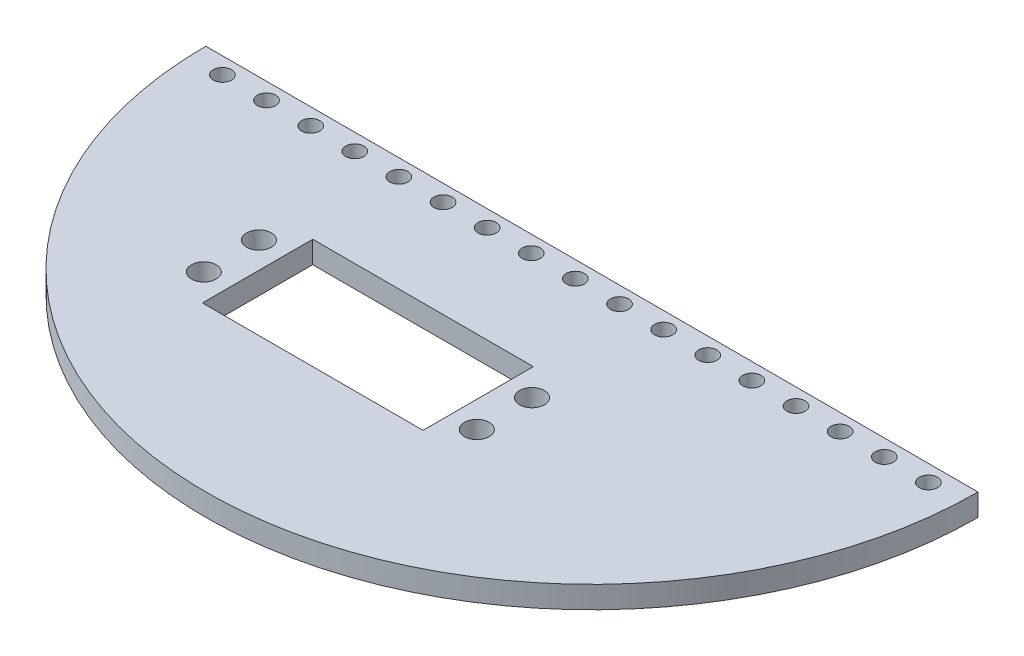
SolidWorks part; units mm, degrees
ref_plane "前视基准面" through (0, 0, 0) normal (0, 0, 1) x (1, 0, 0)
ref_plane "上视基准面" through (0, 0, 0) normal (0, 1, 0) x (1, 0, 0)
ref_plane "右视基准面" through (0, 0, 0) normal (1, 0, 0) x (0, 0, -1)
sketch "草图1" plane through (0, 0, 0) normal (0, 1, 0) x (1, 0, 0)
  line L0 (-50, 0) -> (50, 0)
  arc A0 (50, 0) -> (-50, 0) centre (0, 0) cw
extrude "凸台-拉伸1" add sketch "草图1" along normal blind 4
sketch "草图2" plane through (0, 4, 0) normal (0, 1, 0) x (1, 0, 0)
  line L2 (0, -10.623) -> (10, -10.623)
  line L3 (10, -10.623) -> (10, -30.623)
  line L4 (10, -30.623) -> (-30, -30.623)
  line L5 (-30, -30.623) -> (-30, -10.623)
  line L6 (-30, -10.623) -> (0, -10.623)
extrude "切除-拉伸1" cut sketch "草图2" against normal blind 10
sketch "草图3" plane through (0, 4, 0) normal (0, 1, 0) x (1, 0, 0)
  circle A0 centre (-34.75, -15.623) radius 2.25
  circle A1 centre (-34.75, -25.623) radius 2.25
  circle A2 centre (14.75, -25.623) radius 2.25
  circle A3 centre (14.75, -15.623) radius 2.25
extrude "切除-拉伸2" cut sketch "草图3" against normal blind 10
sketch "草图4" plane through (0, 4, 0) normal (0, 1, 0) x (1, 0, 0)
  circle A0 centre (0, -3) radius 1.65
  circle A1 centre (8, -3) radius 1.65
  circle A2 centre (16, -3) radius 1.65
  circle A3 centre (24, -3) radius 1.65
  circle A4 centre (32, -3) radius 1.65
  circle A5 centre (40, -3) radius 1.65
  circle A6 centre (-40, -3) radius 1.65
  circle A7 centre (-32, -3) radius 1.65
  circle A8 centre (-24, -3) radius 1.65
  circle A9 centre (-16, -3) radius 1.65
  circle A10 centre (-8, -3) radius 1.65
extrude "切除-拉伸3" cut sketch "草图4" against normal blind 10
sketch "草图5" plane through (0, 4, 0) normal (0, 1, 0) x (1, 0, 0)
  line L0 (-70, 0) -> (70, 0)
  circle A0 centre (0, 0) radius 70
  circle A1 centre (0, 0) radius 50
  arc M20 (-50, 0) -> (50, 0) centre (0, 0) ccw
extrude "凸台-拉伸2" add sketch "草图5" against normal blind 4 contours L0 A0 M20 region at (-60, 4, 1.5652)
sketch "草图6" plane through (0, 4, 0) normal (0, 1, 0) x (1, 0, 0)
  circle A0 centre (0, -3) radius 1.65
  circle A1 centre (8, -3) radius 1.65
  circle A2 centre (16, -3) radius 1.65
  circle A3 centre (24, -3) radius 1.65
  circle A4 centre (32, -3) radius 1.65
  circle A5 centre (40, -3) radius 1.65
  circle A6 centre (48, -3) radius 1.65
  circle A7 centre (56, -3) radius 1.65
  circle A8 centre (64, -3) radius 1.65
  circle A9 centre (-8, -3) radius 1.65
  circle A10 centre (-16, -3) radius 1.65
  circle A11 centre (-24, -3) radius 1.65
  circle A12 centre (-32, -3) radius 1.65
  circle A13 centre (-40, -3) radius 1.65
  circle A14 centre (-48, -3) radius 1.65
  circle A15 centre (-56, -3) radius 1.65
  circle A16 centre (-64, -3) radius 1.65
  dimension "D1" = 9
  dimension "D2" = 8
extrude "切除-拉伸4" cut sketch "草图6" against normal blind 4
sketch "草图7" plane through (0, 4, 0) normal (0, 1, 0) x (1, 0, 0)
  line L1 (-30, -20.623) -> (-30, -30.623)
  line L2 (10, -20.623) -> (10, -30.623)
  line L3 (-30, -30.623) -> (10, -30.623)
  line L4 (-30, -10.623) -> (-30, -30.623) construction
  line L5 (10, -30.623) -> (10, -10.623) construction
  line L7 (-30, -20.623) -> (10, -20.623)
  line L8 (-30, -20.623) -> (-30, -40.623)
  line L9 (10, -20.623) -> (10, -40.623)
  line L10 (-30, -40.623) -> (10, -40.623)
  line L11 (-34.75, -15.623) -> (14.75, -15.623)
  line L12 (14.75, -15.623) -> (14.75, -25.623)
  line L13 (14.75, -25.623) -> (14.75, -35.623)
  line L14 (-34.75, -15.623) -> (-34.75, -25.623)
  line L15 (-34.75, -25.623) -> (-34.75, -35.623)
  circle A1 centre (-34.75, -35.623) radius 2.25
  circle A2 centre (14.75, -35.623) radius 2.25
  line M30 (10, -30.623) -> (-30, -30.623)
extrude "切除-拉伸5" cut sketch "草图7" against normal blind 4 contours A1 | L8 L10 L9 M30 | A2 region at (-10, 4, 35.623) region at (16.296, 4, 34.0771) region at (-33.204, 4, 34.0771)
sketch "草图8" plane through (0, 4, 0) normal (0, 1, 0) x (1, 0, 0)
  line L0 (-34.75, -15.623) -> (14.75, -15.623)
  line L1 (14.75, -15.623) -> (14.75, -25.623)
  line L2 (14.75, -25.623) -> (14.75, -20.623)
  line L3 (14.75, -20.623) -> (-41.5549, -20.623)
  line L4 (-41.5549, -20.623) -> (-41.5549, -8.5064)
  line L5 (-41.5549, -8.5064) -> (21.0409, -8.9873)
  line L6 (21.0409, -8.9873) -> (21.0409, -20.623)
  line L7 (21.0409, -20.623) -> (14.75, -20.623)
  line M3 (-30, -40.623) -> (-30, -10.623)
  line M4 (-30, -10.623) -> (10, -10.623)
  line M5 (10, -10.623) -> (10, -40.623)
  circle M24 centre (14.75, -15.623) radius 2.25
  circle M27 centre (-34.75, -15.623) radius 2.25
extrude "凸台-拉伸4" add sketch "草图8" against normal blind 4 contours M27 | L3 L0 M5 M3 | L1 L0 M24 | L0 L1 M24 | L0 M3 M5 M4 region at (-10, 4, 13.123) region at (-10, 4, 18.123) region at (-36.9364, 4, 15.623) region at (15.0683, 4, 15.3047) region at (13.7951, 4, 16.578)
sketch "草图9" plane through (0, 4, 0) normal (0, 1, 0) x (1, 0, 0)
  line L0 (0, -70) -> (0, -80)
  line L1 (0, -80) -> (-10, -80)
  line L2 (-10, -80) -> (10, -80)
  line L3 (80, -80) -> (77, -80)
  line L4 (80, -10) -> (80, -150)
  arc A0 (-70, 0) -> (70, 0) centre (0, 0) ccw construction
  arc A1 (80, -10) -> (80, -150) centre (80, -80) ccw
  circle A2 centre (77, -80) radius 1.65
  circle A3 centre (77, -72) radius 1.65
  circle A4 centre (77, -64) radius 1.65
  circle A5 centre (77, -56) radius 1.65
  circle A6 centre (77, -48) radius 1.65
  circle A7 centre (77, -40) radius 1.65
  circle A8 centre (77, -32) radius 1.65
  circle A9 centre (77, -24) radius 1.65
  circle A10 centre (77, -16) radius 1.65
  circle A11 centre (77, -88) radius 1.65
  circle A12 centre (77, -96) radius 1.65
  circle A13 centre (77, -104) radius 1.65
  circle A14 centre (77, -112) radius 1.65
  circle A15 centre (77, -120) radius 1.65
  circle A16 centre (77, -128) radius 1.65
  circle A17 centre (77, -136) radius 1.65
  circle A18 centre (77, -144) radius 1.65
  dimension "D1" = 9
  dimension "D2" = 9
